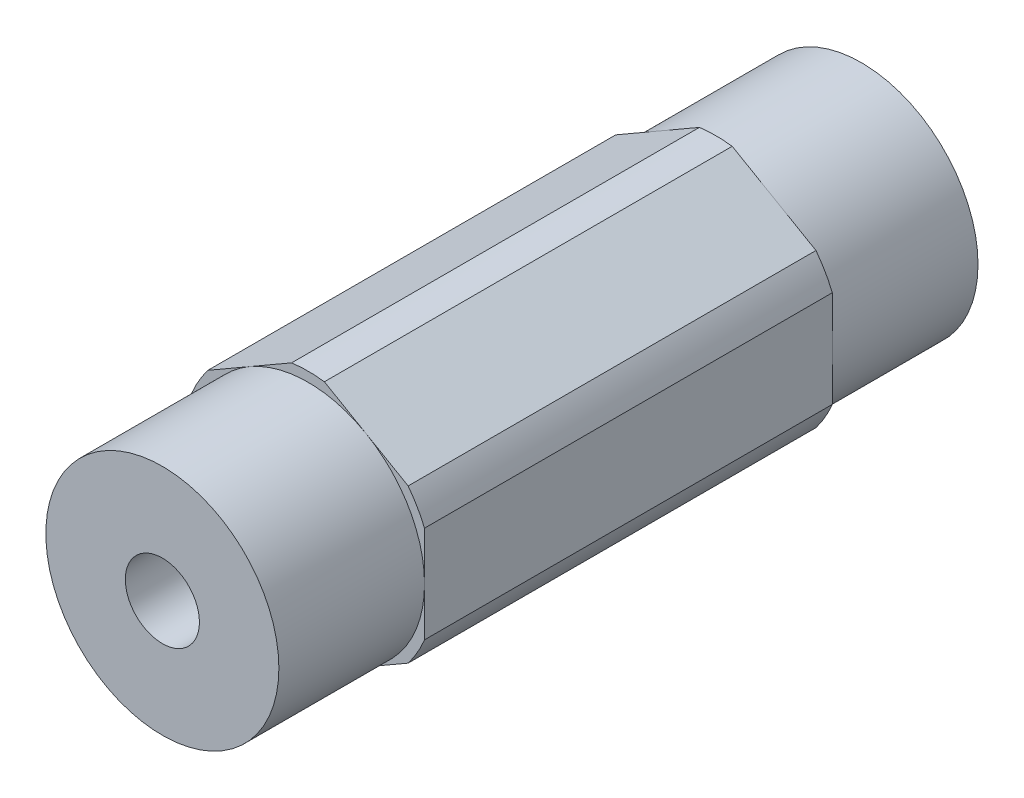
SolidWorks part; units mm, degrees
material "7075-T6 (SN)"
ref_plane "Front Plane" through (0, 0, 0) normal (0, 0, 1) x (1, 0, 0)
ref_plane "Top Plane" through (0, 0, 0) normal (0, 1, 0) x (1, 0, 0)
ref_plane "Right Plane" through (0, 0, 0) normal (1, 0, 0) x (0, 0, -1)
sketch "Sketch1" plane through (0, 0, 0) normal (0, 0, 1) x (1, 0, 0)
  line L1 (0, 7.3323) -> (-6.35, 3.6662)
  line L2 (-6.35, 3.6662) -> (-6.35, -3.6662)
  line L3 (-6.35, -3.6662) -> (0, -7.3323)
  line L4 (0, -7.3323) -> (6.35, -3.6662)
  line L5 (6.35, -3.6662) -> (6.35, 3.6662)
  line L6 (6.35, 3.6662) -> (0, 7.3323)
  circle A0 centre (0, 0) radius 6.35 construction
  circle A1 centre (0, 0) radius 6.875
  circle A2 centre (0, 0) radius 2.0193
  dimension "D1" = 12.7
  dimension "D2" = 4.0386
  dimension "D3" = 13.75
extrude "Boss-Extrude1" add sketch "Sketch1" along normal mid plane 38.1 contours L5 A1 L6 L1 L2 L3 L4 A2 region at (0, 6.6878, 0)
hole_wizard "#10-32 Tapped Hole1" positions "3DSketch2" profile "Sketch3" tap size "#10-32" standard "ANSI Inch"
sketch3d "3DSketch2"
  circle A0 centre (0, 0, -19.05) radius 2.0193 construction
  circle A1 centre (0, 0, 19.05) radius 2.0193 construction
  point P0 (0, 0, 19.05)
  point P2 (0, 0, -19.05)
  point P7 (0, 0, -17.0307)
  point P10 (0, 0, 21.0693)
sketch "Sketch3" plane through (0, 0, 19.05) normal (1, 0, 0) x (0, -1, 0)
  line L0 (0, 0) -> (0, 13.2428)
  line L1 (0, 13.2428) -> (2.0193, 12.0294)
  line L2 (2.0193, 12.0294) -> (2.0193, 0)
  line L5 (2.0193, 0) -> (0, 0)
  line L10 (0, 13.2428) -> (-2.0193, 12.0294) construction
  line L11 (0, -6.35) -> (0, 107.95) construction
  dimension "Tap Drill Dia." = 4.0386
  dimension "Tap Drill Depth" = 12.0294
  dimension "Drill Angle" = 118
cosmetic thread "Hole Thread1" parameters "D1"=9.652, "D2"=4.826
cosmetic thread "Hole Thread2" parameters "D1"=9.652, "D2"=4.826
sketch "Sketch5" plane through (0, 0, 19.05) normal (0, 0, 1) x (1, 0, 0)
  circle A0 centre (0, 0) radius 6.875
  circle A1 centre (0, 0) radius 6.35
  arc A2 (0.893, 6.8168) -> (-0.893, 6.8168) centre (0, 0) ccw construction
  dimension "D1" = 12.7
extrude "Cut-Extrude1" cut sketch "Sketch5" against normal blind 7.9375
mirror "Mirror1" about plane through (0, 0, 0) normal (0, 0, 1) of "Cut-Extrude1"
equation "\"D3@Sketch1\"=13.75mm"
